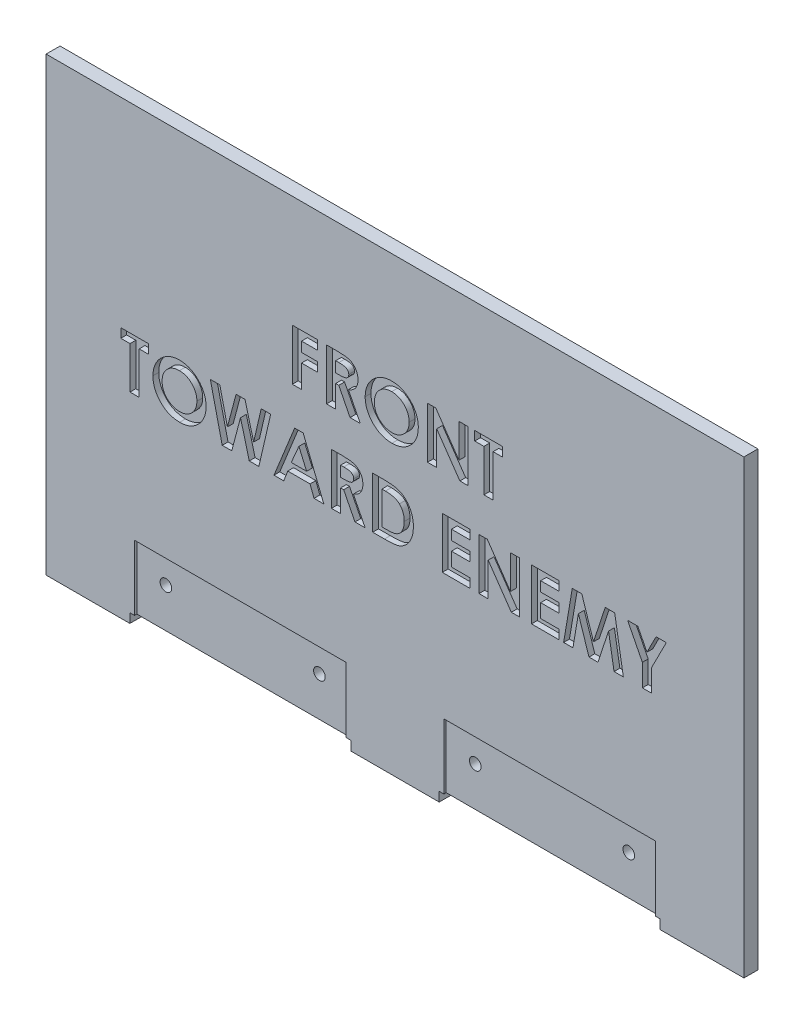
SolidWorks part; units mm, degrees
material "PLA Filament Green"
ref_plane "Alzado" through (0, 0, 0) normal (0, 0, 1) x (1, 0, 0)
ref_plane "Planta" through (0, 0, 0) normal (0, 1, 0) x (1, 0, 0)
ref_plane "Vista lateral" through (0, 0, 0) normal (1, 0, 0) x (0, 0, -1)
sketch "Croquis1" plane through (0, 0, 0) normal (0, 0, 1) x (1, 0, 0)
  line L0 (-75, 47.5) -> (75, -47.5) construction
  line L1 (-75, -47.5) -> (75, -47.5)
  line L2 (-75, -47.5) -> (-75, 47.5)
  line L3 (-75, 47.5) -> (75, 47.5)
  line L4 (75, -47.5) -> (75, 47.5)
  dimension "D1" = 95
  dimension "D2" = 150
extrude "Saliente-Extruir1" add sketch "Croquis1" along normal blind 3
sketch "Croquis2" plane through (0, 0, 3) normal (0, 0, 1) x (1, 0, 0)
  line L0 (-75, -47.5) -> (75, -47.5) construction
  line L1 (-55.75, -47.5) -> (-10.75, -47.5) construction
  line L2 (-55.75, -47.5) -> (-55.75, -33.5) construction
  line L3 (-55.75, -33.5) -> (-10.75, -33.5) construction
  line L4 (-10.75, -47.5) -> (-10.75, -33.5) construction
  line L5 (0, -47.5) -> (0, 28.0467) construction
  line L6 (-33.25, -33.5) -> (-33.25, -47.5) construction
  line L7 (-75, 47.5) -> (-75, -47.5) construction
  circle A0 centre (-49.75, -39) radius 1.25
  circle A1 centre (-16.75, -39) radius 1.25
  dimension "D4" = 2.5
  dimension "D1" = 19.25
  dimension "D2" = 45
  dimension "D3" = 14
  dimension "D5" = 6
  dimension "D6" = 8.5
extrude "Cortar-Extruir1" cut sketch "Croquis2" against normal through all contours A0 | A1
mirror "Simetría1" about plane through (0, 0, 0) normal (1, 0, 0) of "Cortar-Extruir1"
sketch "Croquis5" plane through (0, 0, 3) normal (0, 0, 1) x (1, 0, 0)
  line L0 (-75, 47.5) -> (-75, -47.5) construction
  line L1 (-56, -47.5) -> (-10.5, -47.5)
  line L2 (-56, -47.5) -> (-56, -33.5)
  line L3 (-56, -33.5) -> (-10.5, -33.5)
  line L4 (-10.5, -47.5) -> (-10.5, -33.5)
  line L5 (0, -47.5) -> (0, 0) construction
  line L6 (10.5, -47.5) -> (10.5, -33.5)
  line L7 (56, -33.5) -> (10.5, -33.5)
  line L8 (56, -47.5) -> (56, -33.5)
  line L9 (56, -47.5) -> (10.5, -47.5)
  line L10 (-75, -47.5) -> (75, -47.5) construction
  dimension "D1" = 14
  dimension "D2" = 19
  dimension "D3" = 45.5
extrude "Cortar-Extruir2" cut sketch "Croquis5" against normal blind 0.5
sketch "Croquis3" plane through (0, 0, 3) normal (0, 0, 1) x (1, 0, 0)
  line L0 (-75, 12.5) -> (75, 12.5) construction
  line L1 (0, 47.5) -> (0, 12.5) construction
  line L2 (75, 47.5) -> (-75, 47.5) construction
  line L3 (-75, 47.5) -> (-75, -47.5) construction
  text T0 "FRONT\r\nTOWARD ENEMY" font "Century Gothic" height 11
  dimension "D1" = 35
extrude "Cut-Extrude1" cut sketch "Croquis3" against normal blind 1.25
sketch "Sketch1" plane through (0, 0, 3) normal (0, 0, 1) x (1, 0, 0)
  line L0 (-10.5, -47.5) -> (10.5, -47.5) construction
  line L1 (-75, -47.5) -> (-57, -47.5)
  line L2 (-75, -47.5) -> (-75, -49.5)
  line L3 (-75, -49.5) -> (-57, -49.5)
  line L4 (-57, -47.5) -> (-57, -49.5)
  line L5 (-9.5, -47.5) -> (9.5, -47.5)
  line L6 (-9.5, -47.5) -> (-9.5, -49.5)
  line L7 (-9.5, -49.5) -> (9.5, -49.5)
  line L8 (0, -47.5) -> (0, -49.5) construction
  line L9 (-10.5, -47.5) -> (-10.5, -33.5) construction
  line L10 (-56, -33.5) -> (-56, -47.5) construction
  line L11 (9.5, -47.5) -> (9.5, -49.5)
  line L12 (57, -47.5) -> (57, -49.5)
  line L13 (75, -49.5) -> (57, -49.5)
  line L14 (75, -47.5) -> (75, -49.5)
  line L15 (75, -47.5) -> (57, -47.5)
  dimension "D1" = 1
  dimension "D2" = 1
  dimension "D3" = 2
extrude "Boss-Extrude1" add sketch "Sketch1" against normal up to surface (3 mm away) up to face at (18, -39, 0)
